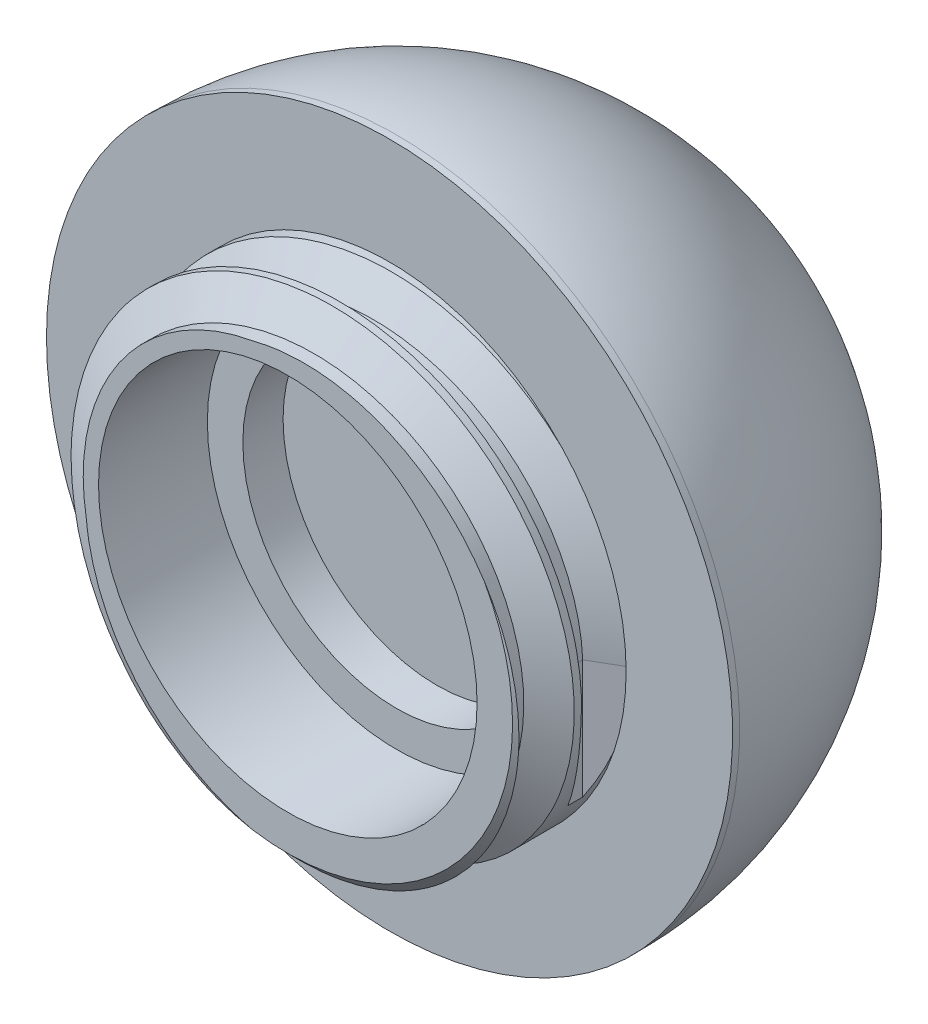
SolidWorks part; units mm, degrees
ref_plane "Front Plane" through (0, 0, 0) normal (0, 0, 1) x (1, 0, 0)
ref_plane "Top Plane" through (0, 0, 0) normal (0, 1, 0) x (1, 0, 0)
ref_plane "Right Plane" through (0, 0, 0) normal (1, 0, 0) x (0, 0, -1)
sketch "Sketch1" plane through (0, 0, 0) normal (0, 1, 0) x (1, 0, 0)
  line L0 (0, 0) -> (0, 36.83)
  line L1 (0, 0) -> (-36.83, 0)
  arc A0 (0, 36.83) -> (-36.83, 0) centre (0, 0) ccw
  dimension "D1" = 73.66
ref_axis "Axis1" through (-20.4556, 0, 0) along (1, 0, 0)
ref_axis "Axis2" through (0, 20.955, 0) along (0, -1, 0)
revolve "Revolve1" add sketch "Sketch1" angle 360 about L0
sketch "Sketch4" plane through (0, 0, 0) normal (0, 0, 1) x (1, 0, 0)
  circle A0 centre (0, 0) radius 25.4
  circle A1 centre (0, 0) radius 20.32
  dimension "D1" = 50.8
  dimension "D2" = 40.64
extrude "Boss-Extrude1" add sketch "Sketch4" along normal blind 11.684
chamfer "Chamfer1" distance 1.27 angle 45 1 edges at (25.4, 0, 11.684)
thread "Thread3" pitch 6.35 method cut profile "Thread Profile4" start angle 0, offset 0, length 0, pitch 6.35, diameter 50.8
ref_plane "Plane4" through (25.4, 0, 0) normal (0, -1, 0) x (1, 0, 0)
sketch "Thread Profile4" plane through (25.4, 0, 0) normal (0, -1, 0) x (1, 0, 0)
  line L0 (0, 0) -> (0, 6.35) construction
  line L11 (0, 0) -> (0, 5.5562)
  line L12 (0, 5.5562) -> (-3.437, 3.5719)
  line L13 (-3.437, 3.5719) -> (-3.437, 1.9844)
  line L15 (-3.437, 1.9844) -> (0, 0)
  line L17 (-3.437, 2.7781) -> (0, 2.7781) construction
  point P2 (0, 0)
  dimension "Pitch" = 6.35
  dimension "Profile_Angle" = 60
  dimension "Profile_Land" = 1.5875
  dimension "Profile_Height" = 3.437
sketch "Sketch18" plane through (0, 0, 0) normal (0, 1, 0) x (1, 0, 0)
  line L4 (25.4, 0) -> (21.963, -1.9844)
  line L5 (21.963, -1.9844) -> (21.963, -3.5719)
  line L6 (21.963, -3.5719) -> (25.4, -5.5562)
  line L7 (25.4, -5.5562) -> (25.4, 0)
  line L8 (25.4, 0) -> (21.963, -1.9844)
  line L9 (21.963, -1.9844) -> (21.963, -3.5719)
  line L10 (21.963, -3.5719) -> (25.4, -5.5562)
  line L11 (25.4, -5.5562) -> (25.4, 0)
  dimension "D1" = 0
extrude "Cut-Extrude2" cut sketch "Sketch18" against normal through all
sketch "Sketch19" plane through (0, 0, 0) normal (0, 0, 1) x (1, 0, 0)
  circle A0 centre (0, 0) radius 16.51
  dimension "D1" = 33.02
extrude "Cut-Extrude3" cut sketch "Sketch19" against normal blind 4.318
sketch "Sketch21" plane through (0, 0, 0) normal (0, 0, 1) x (1, 0, 0)
  circle A0 centre (0, 0) radius 25.4
  circle A1 centre (0, 0) radius 36.83
extrude "Boss-Extrude2" add sketch "Sketch21" along normal blind 0.762
